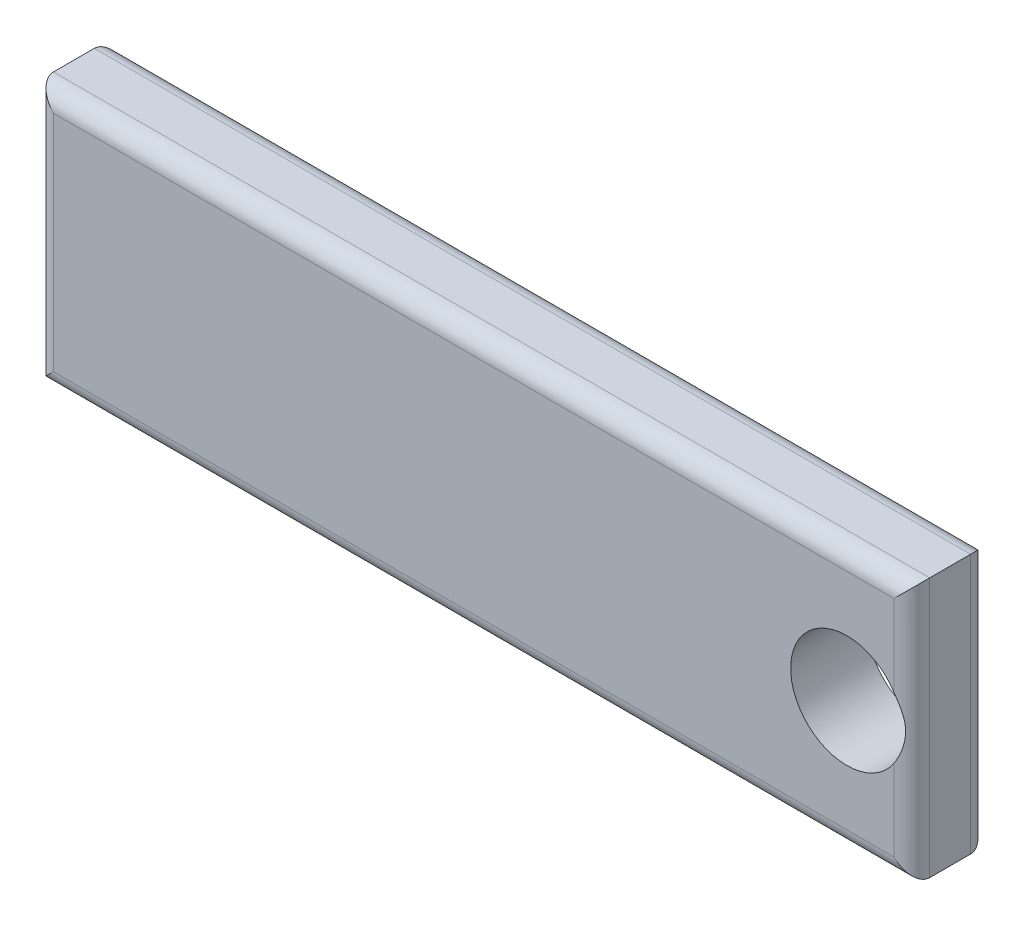
SolidWorks part; units mm, degrees
ref_plane "Front Plane" through (0, 0, 0) normal (0, 0, 1) x (1, 0, 0)
ref_plane "Top Plane" through (0, 0, 0) normal (0, 1, 0) x (1, 0, 0)
ref_plane "Right Plane" through (0, 0, 0) normal (1, 0, 0) x (0, 0, -1)
sketch "Sketch1" plane through (0, 0, 0) normal (0, 0, 1) x (1, 0, 0)
  line L1 (0, 10.16) -> (34.29, 10.16)
  line L2 (0, 10.16) -> (0, 0)
  line L3 (0, 0) -> (34.29, 0)
  line L4 (34.29, 10.16) -> (34.29, 0)
  circle A0 centre (31.75, 5.08) radius 2.2
  dimension "D6" = 4.4
  dimension "D1" = 0
  dimension "D2" = 34.29
  dimension "D3" = 10.16
  dimension "D4" = 5.08
  dimension "D5" = 2.54
extrude "Boss-Extrude1" add sketch "Sketch1" along normal blind 3
fillet "Fillet1" radius 0.7 8 edges at (0, 5.08, 3) (0, 5.08, 0) (34.29, 5.08, 0) (34.29, 5.08, 3) (17.145, 0, 0) (17.145, 10.16, 0) (17.145, 0, 3) (17.145, 10.16, 3)
